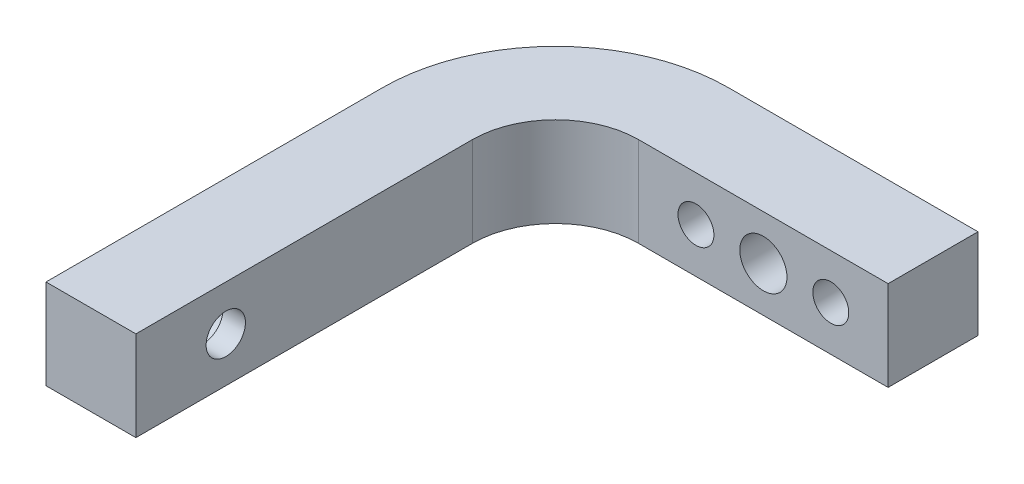
SolidWorks part; units mm, degrees
ref_plane "Front Plane" through (0, 0, 0) normal (0, 0, 1) x (1, 0, 0)
ref_plane "Top Plane" through (0, 0, 0) normal (0, 1, 0) x (1, 0, 0)
ref_plane "Right Plane" through (0, 0, 0) normal (1, 0, 0) x (0, 0, -1)
ref_axis "Z" through (0, 0, -2.267) along (0, 0, 1)
sketch "Sketch1" plane through (0, 0, 0) normal (0, 1, 0) x (1, 0, 0)
  line L0 (-11.1, 0) -> (11.1, 0)
  line L1 (-26.5, -15.4) -> (-26.5, -45.34)
  line L2 (-26.5, -45.34) -> (-18.5, -45.34)
  line L3 (-18.5, -45.34) -> (-18.5, -15.4)
  line L4 (-11.1, -8) -> (11.1, -8)
  line L5 (0, -8) -> (0, 0) construction
  line L6 (18.5, -45.34) -> (18.5, -15.4) construction
  line L7 (26.5, -45.34) -> (18.5, -45.34) construction
  line L8 (26.5, -15.4) -> (26.5, -45.34) construction
  line L9 (11.1, 0) -> (11.1, -8)
  arc A0 (-11.1, 0) -> (-26.5, -15.4) centre (-11.1, -15.4) ccw
  arc A1 (-18.5, -15.4) -> (-11.1, -8) centre (-11.1, -15.4) cw
  arc A2 (18.5, -15.4) -> (11.1, -8) centre (11.1, -15.4) ccw construction
  arc A3 (11.1, 0) -> (26.5, -15.4) centre (11.1, -15.4) cw construction
  dimension "D3" = 7.4
  dimension "D1" = 37
  dimension "D2" = 8
  dimension "D4" = 37.34
extrude "Boss-Extrude1" add sketch "Sketch1" along normal blind 4 and the other way blind 4
sketch "Sketch2" plane through (-18.5, 0, 0) normal (-1, 0, 0) x (0, 0, 1)
  line L1 (20.68, 0) -> (-20.68, 0) construction
  line L2 (0, -4.4) -> (0, 4.4) construction
  circle A0 centre (37.34, 0) radius 1.75
  dimension "D1" = 3.5
  dimension "D2" = 37.34
extrude "Cut-Extrude1" cut sketch "Sketch2" against normal through all both and the other way through all
ref_axis "Axis2" through (-60.1767, 0, 37.34) along (1, 0, 0)
sketch "Sketch3" plane through (0, 0, 0) normal (0, 0, -1) x (-1, 0, 0)
  line L0 (-6, 0) -> (6, 0) construction
  circle A0 centre (0, 0) radius 2.1
  circle A1 centre (-6, 0) radius 1.6
  circle A2 centre (6, 0) radius 1.6
  dimension "D1" = 4.2
  dimension "D3" = 3.2
  dimension "D2" = 12
extrude "Cut-Extrude2" cut sketch "Sketch3" against normal through all
sketch "Sketch4" plane through (-26.5, 0, 0) normal (1, 0, 0) x (0, 0, -1)
  circle A0 centre (-37.34, 0) radius 2.275
  circle A1 centre (-37.34, 0) radius 1.75 construction
  dimension "D1" = 4.55
extrude "Cut-Extrude3" cut sketch "Sketch4" along normal blind 6
sketch "Sketch5" plane through (-26.5, 0, 0) normal (-1, 0, 0) x (0, 0, 1)
  circle A0 centre (37.34, 0) radius 3.825
  point P2 (0, 0)
  dimension "D1" = 7.65
extrude "Cut-Extrude4" cut sketch "Sketch5" against normal blind 0.75
equation "\"width\"= \"EyeDiameter\" + \"EyeClearance\""
equation "\"prongwidth\"= 8"
equation "\"D2@Sketch1\"=\"prongwidth\""
equation "\"D3@Sketch1\"=\"width\"/5"
equation "\"pronglength\"= \"BasePlaneDistance\"'model implicitly adds clearance (of prongwidth) to the hole drilled at the baseplanedistance"
equation "\"D4@Sketch1\"=\"pronglength\""
equation "\"D1@Boss-Extrude1\"=\"prongwidth\"/2"
equation "\"D2@Boss-Extrude1\"=\"prongwidth\"/2"
equation "\"lbracket-plane-to-axis\"= \"BasePlaneDistance\""
equation "\"D2@Sketch2\"=\"lbracket-plane-to-axis\""
equation "\"EyeDiameter\" = 35"
equation "\"BasePlaneDistance\" = \"EyeDiameter\"/2+19.84"
equation "\"EyeClearance\" = 2"
equation "\"D1@Sketch1\"=\"EyeDiameter\"+\"EyeClearance\""
equation "\"BearingDepth\"= 6"
equation "\"BearingHousingID\"=4.5"
equation "\"D1@Sketch4\"=\"BearingHousingID\" + \"PrinterFilamentThickness\" * \"ApplyPrinterOffset\" / 2"
equation "\"D1@Cut-Extrude3\"=\"BearingDepth\""
equation "\"BearingFlangeThickness\"= 0.75"
equation "\"BearingFlangeOD\"=7.5"
equation "\"D1@Sketch5\"=\"BearingFlangeOD\" + \"PrinterFilamentThickness\"*1.5 *\"ApplyPrinterOffset\""
equation "\"D1@Cut-Extrude4\"=\"BearingFlangeThickness\""
equation "\"PrinterFilamentThickness\"= 0.1"
equation "\"ApplyPrinterOffset\"= 1'if 1, adjust hole sizes to try and make pressfits work with the 3d printer"
